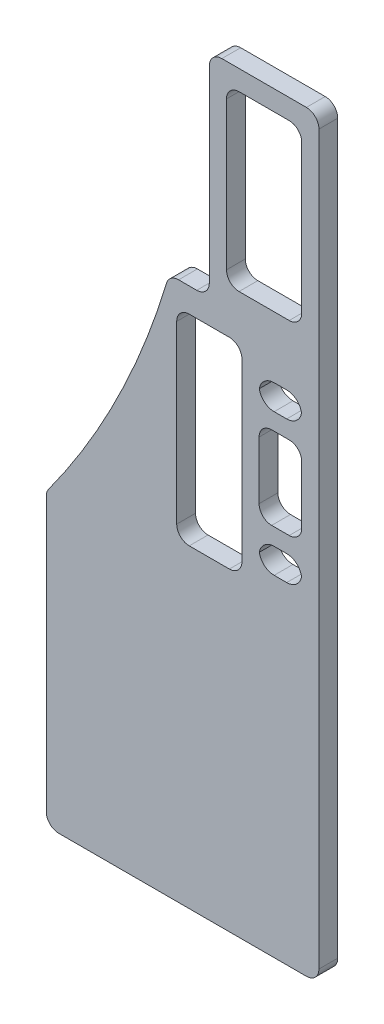
SolidWorks part; units mm, degrees
material "PE High Density Film"
ref_plane "Front Plane" through (0, 0, 0) normal (0, 0, 1) x (1, 0, 0)
ref_plane "Top Plane" through (0, 0, 0) normal (0, 1, 0) x (1, 0, 0)
ref_plane "Right Plane" through (0, 0, 0) normal (1, 0, 0) x (0, 0, -1)
sketch "Sketch1" plane through (0, 0, 0) normal (0, 0, 1) x (1, 0, 0)
  line L1 (-54.35, 150) -> (54.35, 150)
  line L2 (-54.35, 150) -> (-54.35, -150)
  line L3 (-54.35, -150) -> (54.35, -150)
  line L4 (54.35, 150) -> (54.35, -150)
  line L5 (-54.35, 150) -> (54.35, -150) construction
  line L6 (-54.35, -150) -> (54.35, 150) construction
  point P0 (0, 0)
  dimension "D1" = 300
  dimension "D2" = 108.7
extrude "Boss-Extrude1" add sketch "Sketch1" along normal blind 7.5
sketch "Sketch2" plane through (0, 0, 7.5) normal (0, 0, 1) x (1, 0, 0)
  line L1 (-54.35, 150) -> (10.65, 150)
  line L2 (-54.35, 150) -> (-54.35, 65)
  line L3 (-54.35, 65) -> (10.65, 65)
  line L4 (10.65, 150) -> (10.65, 65)
  dimension "D1" = 65
  dimension "D2" = 85
extrude "Cut-Extrude1" cut sketch "Sketch2" against normal blind 7.5
ref_plane "Plane1" through (10.65, 65, 7.5) normal (1, 0, 0) x (0, 0, -1)
sketch "Sketch4" plane through (0, 0, 7.5) normal (0, 0, 1) x (1, 0, 0)
  line L4 (10.65, 150) -> (-309.35, 153.0005) construction
  line L5 (-54.35, 65) -> (-54.35, -34.4755)
  line L6 (-54.35, 65) -> (-54.35, -150) construction
  line L7 (-54.35, 65) -> (-5.33, 65)
  line L8 (-54.35, 65) -> (10.65, 65) construction
  arc A1 (-54.35, -34.4755) -> (-5.33, 65) centre (-309.35, 153.0005) ccw
  dimension "D2" = 633
  dimension "D3" = 99.4755
  dimension "D1" = 320
extrude "Cut-Extrude2" cut sketch "Sketch4" against normal blind 7.5
sketch "Sketch5" plane through (0, 0, 7.5) normal (0, 0, 1) x (1, 0, 0)
  line L0 (10.65, 150) -> (10.65, 65) construction
  line L1 (10.65, 107.5) -> (54.35, 107.5) construction
  line L2 (54.35, -150) -> (54.35, 150) construction
  line L4 (17.5, 142) -> (47.5, 142)
  line L5 (17.5, 142) -> (17.5, 73)
  line L6 (17.5, 73) -> (47.5, 73)
  line L7 (47.5, 142) -> (47.5, 73)
  line L8 (17.5, 142) -> (47.5, 73) construction
  line L9 (17.5, 73) -> (47.5, 142) construction
  point P8 (32.5, 107.5)
  dimension "D1" = 30
  dimension "D2" = 69
extrude "Cut-Extrude3" cut sketch "Sketch5" against normal blind 7.5
sketch "Sketch6" plane through (0, 0, 7.5) normal (0, 0, 1) x (1, 0, 0)
  line L0 (-5.33, 65) -> (54.35, 65) construction
  line L1 (54.35, -150) -> (54.35, 150) construction
  line L2 (-54.35, -34.4755) -> (54.35, -34.4755) construction
  line L3 (-5.33, 65) -> (24.51, 65) construction
  line L4 (10.65, 65) -> (10.65, -34.4755) construction
  line L10 (-2.35, 55.2622) -> (23.65, 55.2622)
  line L11 (-2.35, 55.2622) -> (-2.35, -24.7378)
  line L12 (-2.35, -24.7378) -> (23.65, -24.7378)
  line L13 (23.65, 55.2622) -> (23.65, -24.7378)
  line L14 (-2.35, 55.2622) -> (23.65, -24.7378) construction
  line L15 (-2.35, -24.7378) -> (23.65, 55.2622) construction
  point P11 (10.65, 15.2622)
  dimension "D1" = 80
  dimension "D2" = 26
extrude "Cut-Extrude4" cut sketch "Sketch6" against normal blind 7.5
sketch "Sketch9" plane through (0, 0, 7.5) normal (0, 0, 1) x (1, 0, 0)
  line L0 (23.65, 15.2622) -> (54.35, 15.2622) construction
  line L1 (23.65, -24.7378) -> (23.65, 55.2622) construction
  line L2 (54.35, -150) -> (54.35, 150) construction
  line L4 (30.5, 31.7622) -> (47.5, 31.7622)
  line L5 (30.5, 31.7622) -> (30.5, -1.2378)
  line L6 (30.5, -1.2378) -> (47.5, -1.2378)
  line L7 (47.5, 31.7622) -> (47.5, -1.2378)
  line L8 (30.5, 31.7622) -> (47.5, -1.2378) construction
  line L9 (30.5, -1.2378) -> (47.5, 31.7622) construction
  point P6 (39, 15.2622)
  dimension "D1" = 17
  dimension "D2" = 33
extrude "Cut-Extrude5" cut sketch "Sketch9" against normal blind 7.5
sketch "Sketch10" plane through (0, 0, 7.5) normal (0, 0, 1) x (1, 0, 0)
  line L0 (23.65, 55.2622) -> (54.35, 55.2622) construction
  line L1 (54.35, -150) -> (54.35, 150) construction
  line L2 (39, 31.7622) -> (39, 55.2622) construction
  line L3 (47.5, 31.7622) -> (30.5, 31.7622) construction
  line L4 (23.65, -24.7378) -> (54.35, -24.7378) construction
  line L5 (30.5, 48.5122) -> (47.5, 48.5122)
  line L6 (30.5, 48.5122) -> (30.5, 38.5122)
  line L7 (30.5, 38.5122) -> (47.5, 38.5122)
  line L8 (47.5, 48.5122) -> (47.5, 38.5122)
  line L9 (30.5, 48.5122) -> (47.5, 38.5122) construction
  line L10 (30.5, 38.5122) -> (47.5, 48.5122) construction
  line L11 (39, -1.2378) -> (39, -24.7378) construction
  line L12 (30.5, -1.2378) -> (47.5, -1.2378) construction
  line L14 (30.5, -7.9878) -> (47.5, -7.9878)
  line L15 (30.5, -7.9878) -> (30.5, -17.9878)
  line L16 (30.5, -17.9878) -> (47.5, -17.9878)
  line L17 (47.5, -7.9878) -> (47.5, -17.9878)
  line L18 (30.5, -7.9878) -> (47.5, -17.9878) construction
  line L19 (30.5, -17.9878) -> (47.5, -7.9878) construction
  point P11 (39, 43.5122)
  point P22 (39, -12.9878)
  dimension "D1" = 10
  dimension "D2" = 17
  dimension "D3" = 17
  dimension "D4" = 10
extrude "Cut-Extrude6" cut sketch "Sketch10" against normal blind 7.5
fillet "Fillet3" radius 5 19 edges at (54.35, -150, 3.75) (-54.35, -150, 3.75) (-54.35, -34.4755, 3.75) (47.5, -1.2378, 3.75) (30.5, -1.2378, 3.75) (30.5, 31.7622, 3.75) (47.5, 31.7622, 3.75) (23.65, -24.7378, 3.75) (-2.35, -24.7378, 3.75) (-2.35, 55.2622, 3.75) (23.65, 55.2622, 3.75) (47.5, 73, 3.75) (17.5, 73, 3.75) (17.5, 142, 3.75) (47.5, 142, 3.75) (-5.33, 65, 3.75) (10.65, 65, 3.75) (54.35, 150, 3.75) (10.65, 150, 3.75)
fillet "Fillet4" radius 6 8 edges at (47.5, -17.9878, 3.75) (47.5, -7.9878, 3.75) (30.5, -17.9878, 3.75) (30.5, -7.9878, 3.75) (47.5, 38.5122, 3.75) (30.5, 38.5122, 3.75) (47.5, 48.5122, 3.75) (30.5, 48.5122, 3.75)
